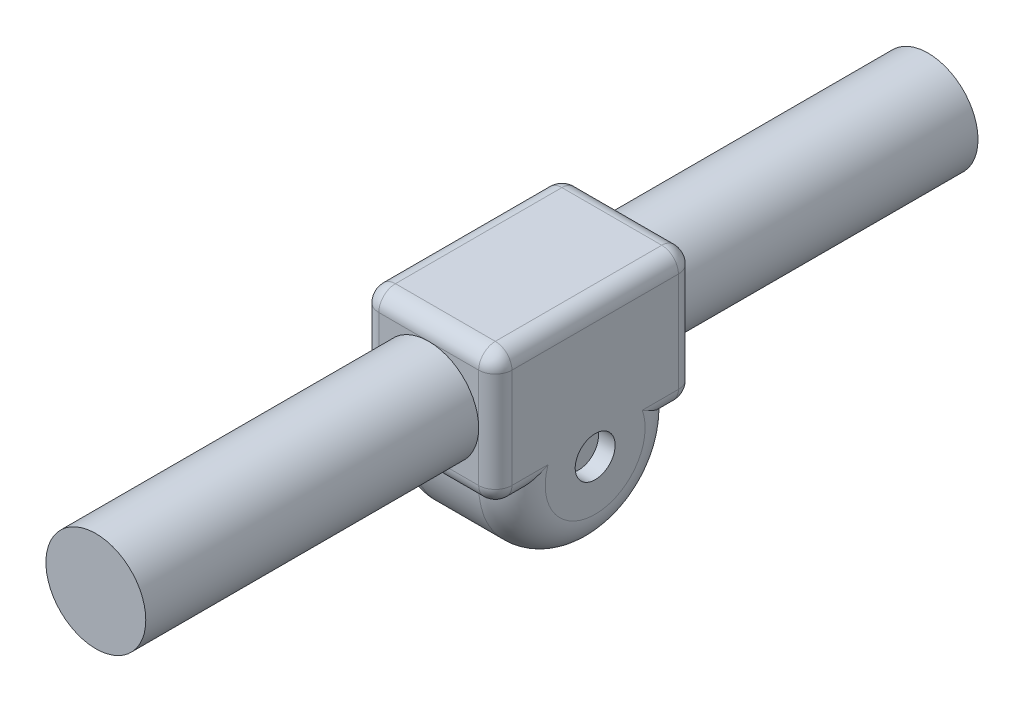
SolidWorks part; units mm, degrees
ref_plane "Front Plane" through (0, 0, 0) normal (0, 0, 1) x (1, 0, 0)
ref_plane "Top Plane" through (0, 0, 0) normal (0, 1, 0) x (1, 0, 0)
ref_plane "Right Plane" through (0, 0, 0) normal (1, 0, 0) x (0, 0, -1)
sketch "Sketch1" plane through (0, 0, 0) normal (1, 0, 0) x (0, 0, -1)
  line L1 (-30, 0) -> (-30, 40)
  line L2 (-30, 40) -> (30, 40)
  line L3 (30, 40) -> (30, 0)
  line L4 (30, 0) -> (25, 0)
  line L5 (-25, 0) -> (-30, 0)
  arc A0 (-25, 0) -> (25, 0) centre (0, 0) ccw
  dimension "D1" = 25
  dimension "D2" = 30
  dimension "D3" = 30
  dimension "D4" = 40
extrude "Boss-Extrude1" add sketch "Sketch1" along normal blind 40
fillet "Fillet1" radius 10 2 edges at (0, -25, 0) (40, -25, 0)
fillet "Fillet2" radius 5 14 edges at (0, 20, -30) (0, 40, 0) (0, 20, 30) (0, 0, 22.5) (0, 0, -22.5) (40, 0, 22.5) (40, 20, 30) (40, 40, 0) (40, 20, -30) (40, 0, -22.5) (20, 0, -30) (20, 0, 30) (20, 40, 30) (20, 40, -30)
sketch "Sketch2" plane through (0, 0, 30) normal (0, 0, 1) x (1, 0, 0)
  circle A0 centre (20, 20) radius 15
  dimension "D1" = 30
extrude "Boss-Extrude2" add sketch "Sketch2" along normal blind 100 and the other way blind 150
sketch "Sketch3" plane through (40, 0, 0) normal (1, 0, 0) x (0, 0, -1)
  circle A0 centre (0, 0) radius 6
  dimension "D1" = 12
extrude "Cut-Extrude1" cut sketch "Sketch3" against normal blind 5
